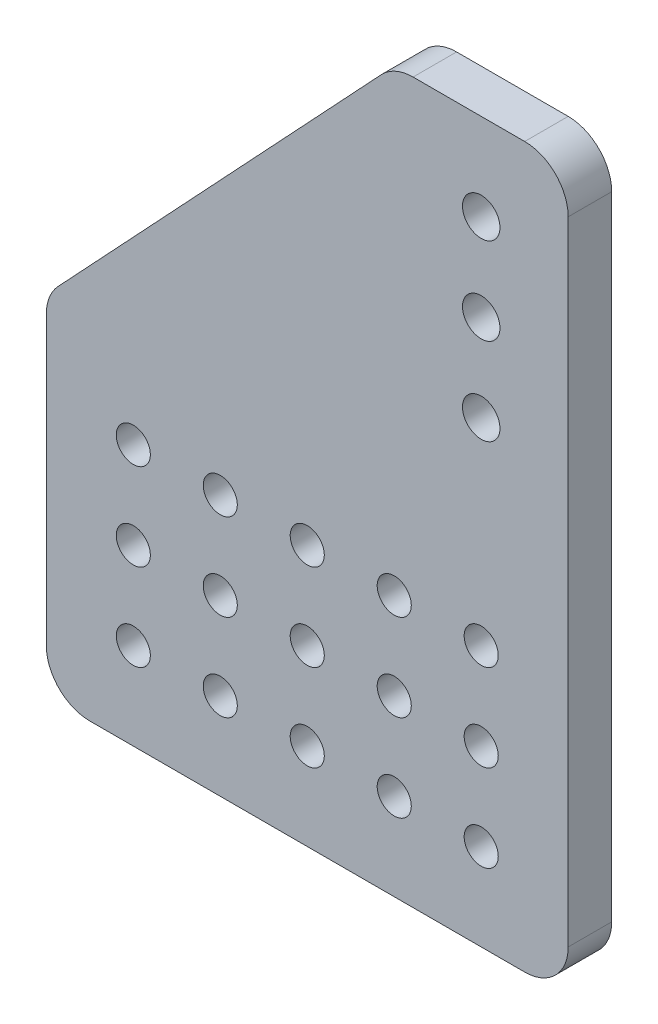
SolidWorks part; units mm, degrees
material "6061-T6 (SS)"
ref_plane "Front Plane" through (0, 0, 0) normal (0, 0, 1) x (1, 0, 0)
ref_plane "Top Plane" through (0, 0, 0) normal (0, 1, 0) x (1, 0, 0)
ref_plane "Right Plane" through (0, 0, 0) normal (1, 0, 0) x (0, 0, -1)
sketch "Sketch1" plane through (0, 0, 0) normal (0, 0, 1) x (1, 0, 0)
  line L0 (-76.2, 0) -> (-25.4, 54.229)
  line L1 (0, 0) -> (-76.2, 0) construction
  line L2 (0, 0) -> (0, -50.8)
  line L3 (0, -50.8) -> (-76.2, -50.8)
  line L4 (-76.2, 0) -> (-76.2, -50.8)
  line L5 (0, 3.429) -> (-25.4, 3.429) construction
  line L6 (0, 3.429) -> (0, 54.229)
  line L7 (0, 54.229) -> (-25.4, 54.229)
  line L8 (-25.4, 3.429) -> (-25.4, 54.229) construction
  line L9 (0, 3.429) -> (0, 0)
  dimension "D1" = 50.8
  dimension "D2" = 76.2
  dimension "D3" = 50.8
  dimension "D4" = 25.4
  dimension "D5" = 3.429
extrude "Boss-Extrude1" add sketch "Sketch1" along normal mid plane 6.35
sketch "Sketch2" plane through (0, 0, 3.175) normal (0, 0, 1) x (1, 0, 0)
  line L0 (-76.2, -50.8) -> (0, -50.8) construction
  line L1 (0, -50.8) -> (0, 54.229) construction
  line L2 (0, 54.229) -> (-25.4, 54.229) construction
  circle A0 centre (-12.7, -38.1) radius 2.4892
  circle A1 centre (-12.7, 41.529) radius 2.7355
  point P10 (0, 0)
  dimension "D1" = 4.9784
  dimension "D2" = 12.7
  dimension "D3" = 12.7
  dimension "D4" = 12.7
extrude "Cut-Extrude1" cut sketch "Sketch2" against normal through all
pattern_linear "LPattern1" count 5 spacing 12.7 along (-1, 0, 0) count 3 spacing 12.7 along (0, 1, 0) of face at (-10.2108, -38.1, -3.175)
pattern_linear "LPattern2" count 3 spacing 12.7 along (0, -1, 0) of face at (-9.9645, 41.529, -3.175)
fillet "Fillet1" radius 6.35 5 edges at (0, -50.8, 0) (-76.2, -50.8, 0) (-76.2, 0, 0) (0, 54.229, 0) (-25.4, 54.229, 0)
